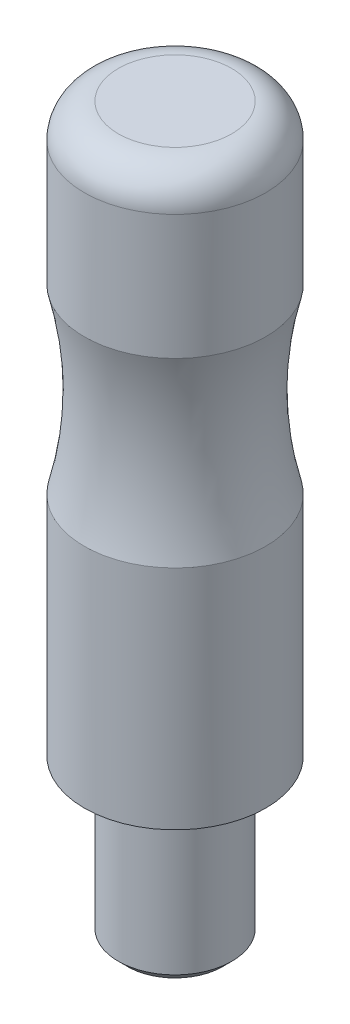
SolidWorks part; units mm, degrees
ref_plane "Front Plane" through (0, 0, 0) normal (0, 0, 1) x (1, 0, 0)
ref_plane "Top Plane" through (0, 0, 0) normal (0, 1, 0) x (1, 0, 0)
ref_plane "Right Plane" through (0, 0, 0) normal (1, 0, 0) x (0, 0, -1)
sketch "Sketch1" plane through (0, 0, 0) normal (0, 1, 0) x (1, 0, 0)
  circle A0 centre (0, 0) radius 4
  dimension "D1" = 8
extrude "Boss-Extrude1" add sketch "Sketch1" along normal blind 25
sketch "Sketch2" plane through (0, 0, 0) normal (0, -1, 0) x (1, 0, 0)
  circle A0 centre (0, 0) radius 2.5
  dimension "D1" = 5
extrude "Boss-Extrude2" add sketch "Sketch2" along normal blind 7
chamfer "Chamfer1" distance 0.4 angle 45 1 edges at (0, -7, -2.5)
fillet "Fillet1" radius 1.5 1 edges at (0, 25, 4)
sketch "Sketch3" plane through (0, 0, 0) normal (0, 0, 1) x (1, 0, 0)
  line L0 (-4, 23.5) -> (-4, 0) construction
  line L1 (-4, 0) -> (4, 0) construction
  line L2 (-4, 18) -> (-5, 18)
  line L3 (-5, 18) -> (-5, 10)
  line L4 (-5, 10) -> (-4, 10)
  line L5 (0, 0) -> (0, 18) construction
  arc A0 (-4, 18) -> (-4, 10) centre (-19.4919, 14) cw
  dimension "D3" = 16
  dimension "D1" = 8
  dimension "D2" = 10
  dimension "D4" = 1
revolve "Cut-Revolve1" cut sketch "Sketch3" angle 360 about L5
